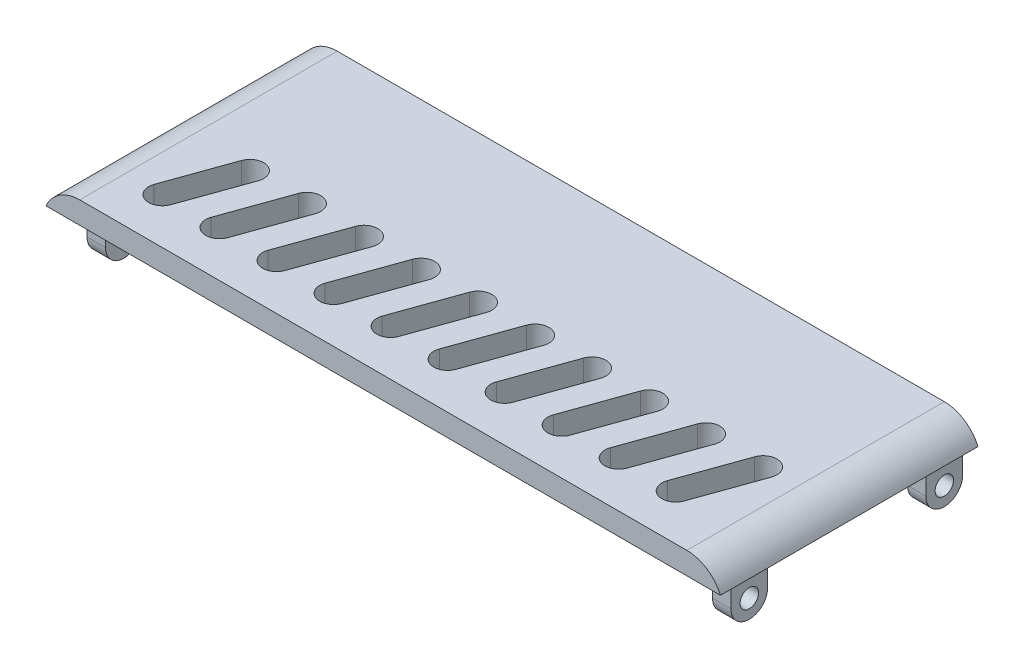
SolidWorks part; units mm, degrees
ref_plane "前视基准面" through (0, 0, 0) normal (0, 0, 1) x (1, 0, 0)
ref_plane "上视基准面" through (0, 0, 0) normal (0, 1, 0) x (1, 0, 0)
ref_plane "右视基准面" through (0, 0, 0) normal (1, 0, 0) x (0, 0, -1)
sketch "草图2" plane through (0, 0, 0) normal (0, 1, 0) x (1, 0, 0)
  line L1 (-31.0872, 15.1404) -> (42.9128, 15.1404)
  line L2 (-31.0872, 15.1404) -> (-31.0872, -12.8596)
  line L3 (-31.0872, -12.8596) -> (42.9128, -12.8596)
  line L4 (42.9128, 15.1404) -> (42.9128, -12.8596)
  dimension "D1" = 74
  dimension "D2" = 28
extrude "凸台-拉伸1" add sketch "草图2" along normal blind 4
fillet "圆角1" radius 4 2 edges at (-31.0872, 4, -1.1404) (42.9128, 4, -1.1404)
sketch "草图3" plane through (0, 0, -15.1404) normal (0, 0, -1) x (-1, 0, 0)
  line L1 (31.0872, 0) -> (-42.9128, 0)
  line L2 (31.0872, 0) -> (31.0872, 1.6)
  line L3 (31.0872, 1.6) -> (-42.9128, 1.6)
  line L4 (-42.9128, 0) -> (-42.9128, 1.6)
  dimension "D1" = 1.6
extrude "切除-拉伸1" cut sketch "草图3" against normal through all
sketch "草图15" plane through (0, 1.6, 0) normal (0, -1, 0) x (1, 0, 0)
  line L0 (33.5789, 9.0596) -> (41.4128, 9.0596)
  line L2 (45.2135, 5.0596) -> (45.2135, 10.0596)
  line L3 (45.2135, 10.0596) -> (33.5789, 10.0596)
  line L4 (33.5789, 9.0596) -> (33.5789, 10.0596)
  line L5 (42.5789, -15.1404) -> (42.5789, 12.8596) construction
  line L6 (41.4128, 9.0596) -> (41.4128, 5.0596)
  line L7 (41.4128, 5.0596) -> (45.2135, 5.0596)
  line L8 (42.9128, 14.8596) -> (42.9128, -17.1404) construction
  line L9 (-30.7532, 12.8596) -> (42.5789, 12.8596) construction
  dimension "D1" = 1
  dimension "D2" = 9
  dimension "D3" = 5
  dimension "D4" = 1.5
  dimension "D5" = 2.8
sketch "草图19" plane through (0, 4, 0) normal (0, 1, 0) x (1, 0, 0)
  line L0 (-20.5872, -0.8596) -> (-23.0872, -7.8596) construction
  line L5 (-19.1746, -1.3641) -> (-21.6746, -8.3641)
  line L8 (-21.9998, -0.3551) -> (-24.4998, -7.3551)
  line L11 (38.9128, 15.1404) -> (-27.0872, 15.1404) construction
  line L14 (-27.0872, -12.8596) -> (38.9128, -12.8596) construction
  line L17 (-14.3872, -0.8596) -> (-16.8872, -7.8596) construction
  line L20 (-12.9746, -1.3641) -> (-15.4746, -8.3641)
  line L23 (-15.7998, -0.3551) -> (-18.2998, -7.3551)
  line L26 (-40.9597, 1.1404) -> (-18.0872, 1.1404) construction
  line L27 (-27.0872, 15.1404) -> (-27.0872, -12.8596) construction
  line L28 (-8.1872, -0.8596) -> (-10.6872, -7.8596) construction
  line L31 (-6.7746, -1.3641) -> (-9.2746, -8.3641)
  line L34 (-9.5998, -0.3551) -> (-12.0998, -7.3551)
  line L37 (-1.9872, -0.8596) -> (-4.4872, -7.8596) construction
  line L40 (-0.5746, -1.3641) -> (-3.0746, -8.3641)
  line L43 (-3.3998, -0.3551) -> (-5.8998, -7.3551)
  line L46 (4.2128, -0.8596) -> (1.7128, -7.8596) construction
  line L49 (5.6254, -1.3641) -> (3.1254, -8.3641)
  line L52 (2.8002, -0.3551) -> (0.3002, -7.3551)
  line L53 (10.4128, -0.8596) -> (7.9128, -7.8596) construction
  line L54 (11.8254, -1.3641) -> (9.3254, -8.3641)
  line L55 (9.0002, -0.3551) -> (6.5002, -7.3551)
  line L56 (16.6128, -0.8596) -> (14.1128, -7.8596) construction
  line L57 (18.0254, -1.3641) -> (15.5254, -8.3641)
  line L58 (15.2002, -0.3551) -> (12.7002, -7.3551)
  line L59 (22.8128, -0.8596) -> (20.3128, -7.8596) construction
  line L60 (24.2254, -1.3641) -> (21.7254, -8.3641)
  line L61 (21.4002, -0.3551) -> (18.9002, -7.3551)
  line L62 (29.0128, -0.8596) -> (26.5128, -7.8596) construction
  line L63 (30.4254, -1.3641) -> (27.9254, -8.3641)
  line L64 (27.6002, -0.3551) -> (25.1002, -7.3551)
  line L65 (35.2128, -0.8596) -> (32.7128, -7.8596) construction
  line L66 (36.6254, -1.3641) -> (34.1254, -8.3641)
  line L67 (33.8002, -0.3551) -> (31.3002, -7.3551)
  arc A32 (-19.1746, -1.3641) -> (-21.9998, -0.3551) centre (-20.5872, -0.8596) ccw
  arc A33 (-24.4998, -7.3551) -> (-21.6746, -8.3641) centre (-23.0872, -7.8596) ccw
  arc A34 (-12.9746, -1.3641) -> (-15.7998, -0.3551) centre (-14.3872, -0.8596) ccw
  arc A35 (-18.2998, -7.3551) -> (-15.4746, -8.3641) centre (-16.8872, -7.8596) ccw
  arc A36 (-6.7746, -1.3641) -> (-9.5998, -0.3551) centre (-8.1872, -0.8596) ccw
  arc A37 (-12.0998, -7.3551) -> (-9.2746, -8.3641) centre (-10.6872, -7.8596) ccw
  arc A38 (-0.5746, -1.3641) -> (-3.3998, -0.3551) centre (-1.9872, -0.8596) ccw
  arc A39 (-5.8998, -7.3551) -> (-3.0746, -8.3641) centre (-4.4872, -7.8596) ccw
  arc A40 (5.6254, -1.3641) -> (2.8002, -0.3551) centre (4.2128, -0.8596) ccw
  arc A41 (0.3002, -7.3551) -> (3.1254, -8.3641) centre (1.7128, -7.8596) ccw
  arc A42 (11.8254, -1.3641) -> (9.0002, -0.3551) centre (10.4128, -0.8596) ccw
  arc A43 (6.5002, -7.3551) -> (9.3254, -8.3641) centre (7.9128, -7.8596) ccw
  arc A44 (18.0254, -1.3641) -> (15.2002, -0.3551) centre (16.6128, -0.8596) ccw
  arc A45 (12.7002, -7.3551) -> (15.5254, -8.3641) centre (14.1128, -7.8596) ccw
  arc A46 (24.2254, -1.3641) -> (21.4002, -0.3551) centre (22.8128, -0.8596) ccw
  arc A47 (18.9002, -7.3551) -> (21.7254, -8.3641) centre (20.3128, -7.8596) ccw
  arc A48 (30.4254, -1.3641) -> (27.6002, -0.3551) centre (29.0128, -0.8596) ccw
  arc A49 (25.1002, -7.3551) -> (27.9254, -8.3641) centre (26.5128, -7.8596) ccw
  arc A50 (36.6254, -1.3641) -> (33.8002, -0.3551) centre (35.2128, -0.8596) ccw
  arc A51 (31.3002, -7.3551) -> (34.1254, -8.3641) centre (32.7128, -7.8596) ccw
  point P2 (-21.8372, -4.3596)
  point P15 (-15.6372, -4.3596)
  point P22 (-9.4372, -4.3596)
  point P29 (-3.2372, -4.3596)
  point P36 (2.9628, -4.3596)
  point P43 (9.1628, -4.3596)
  point P50 (15.3628, -4.3596)
  point P57 (21.5628, -4.3596)
  point P64 (-27.0872, 1.1404)
  point P68 (27.7628, -4.3596)
  point P75 (33.9628, -4.3596)
  dimension "D6" = 4
  dimension "D3" = 1.5
  dimension "D1" = 16
  dimension "D2" = 5
  dimension "D4" = 6.5
  dimension "D5" = 10
extrude "切除-拉伸6" cut sketch "草图19" against normal up to next
sketch "草图21" plane through (0, 1.6, 0) normal (0, -1, 0) x (1, 0, 0)
  line L1 (-22.7532, 12.0596) -> (-12.7532, 12.0596)
  line L2 (-22.7532, 12.0596) -> (-22.7532, 10.0596)
  line L3 (-22.7532, 10.0596) -> (-12.7532, 10.0596)
  line L4 (-12.7532, 12.0596) -> (-12.7532, 10.0596)
  line L5 (30.5789, 10.0596) -> (18.5789, 10.0596)
  line L6 (30.5789, 10.0596) -> (30.5789, 12.0596)
  line L7 (30.5789, 12.0596) -> (18.5789, 12.0596)
  line L8 (18.5789, 10.0596) -> (18.5789, 12.0596)
  line L12 (-30.7532, 12.8596) -> (-30.7532, -15.1404) construction
  dimension "D1" = 2
  dimension "D2" = 8
  dimension "D3" = 10
  dimension "D4" = 12
extrude "凸台-拉伸9" add sketch "草图21" along normal blind 0.15
sketch "草图22" plane through (0, 1.6, 0) normal (0, -1, 0) x (1, 0, 0)
  line L1 (-29.0872, 10.0596) -> (-27.0872, 10.0596)
  line L2 (-29.0872, 10.0596) -> (-29.0872, 6.0596)
  line L3 (-29.0872, 6.0596) -> (-27.0872, 6.0596)
  line L4 (-27.0872, 10.0596) -> (-27.0872, 6.0596)
  line L5 (-29.0872, -1.1802) -> (-29.0872, -15.1404) construction
  line L6 (-29.0872, -11.1404) -> (-27.0872, -11.1404)
  line L7 (-29.0872, -11.1404) -> (-29.0872, -15.1404)
  line L8 (-29.0872, -15.1404) -> (-27.0872, -15.1404)
  line L9 (-27.0872, -11.1404) -> (-27.0872, -15.1404)
  line L10 (-30.7532, -15.1404) -> (42.5789, -15.1404) construction
  line L11 (-30.7532, 12.8596) -> (42.5789, 12.8596) construction
  line L12 (40.9128, -15.1404) -> (40.9128, -1.1802) construction
  line L13 (40.9128, 10.0596) -> (38.9128, 10.0596)
  line L14 (40.9128, 10.0596) -> (40.9128, 6.0596)
  line L15 (40.9128, 6.0596) -> (38.9128, 6.0596)
  line L16 (38.9128, 10.0596) -> (38.9128, 6.0596)
  line L17 (40.9128, -15.1404) -> (38.9128, -15.1404)
  line L18 (40.9128, -15.1404) -> (40.9128, -11.1404)
  line L19 (40.9128, -11.1404) -> (38.9128, -11.1404)
  line L20 (38.9128, -15.1404) -> (38.9128, -11.1404)
  line L21 (40.9128, 5.8198) -> (40.9128, 12.8596) construction
  line L22 (-29.0872, 12.8596) -> (-29.0872, 5.8198) construction
  point P4 (-29.0872, 12.8596)
  point P21 (0, 0)
  point P25 (0, 0)
  point P26 (0, 0)
  point P27 (40.9128, 9.9538)
  point P28 (40.9128, 10.0899)
  point P29 (40.9128, 8.8596)
  point P30 (0, 0)
  point P33 (0, 0)
  point P37 (0, 0)
  point P38 (-29.0872, 11.7548)
  dimension "D1" = 4
  dimension "D2" = 2
  dimension "D3" = 2.8
extrude "凸台-拉伸10" add sketch "草图22" along normal blind 5.5
fillet "圆角3" radius 2 8 edges at (-28.0872, -3.9, -15.1404) (-28.0872, -3.9, -11.1404) (-28.0872, -3.9, 6.0596) (-28.0872, -3.9, 10.0596) (39.9128, -3.9, -11.1404) (39.9128, -3.9, -15.1404) (39.9128, -3.9, 6.0596) (39.9128, -3.9, 10.0596)
sketch "草图23" plane through (-29.0872, 0, 0) normal (-1, 0, 0) x (0, 0, 1)
  circle A0 centre (8.0596, -1.9) radius 1
  circle A1 centre (-13.1404, -1.9) radius 1
  dimension "D1" = 2
extrude "切除-拉伸8" cut sketch "草图23" against normal blind 2 draft 2
sketch "草图24" plane through (40.9128, 0, 0) normal (1, 0, 0) x (0, 0, -1)
  circle A0 centre (13.1404, -1.9) radius 1 construction
  circle A2 centre (13.1404, -1.9) radius 1
  circle A3 centre (-8.0596, -1.9) radius 1
  point P2 (-10.8596, -1.9)
  point P3 (-8.0596, -1.9)
  point P6 (0, 0)
  point P7 (-10.8596, -1.9)
  point P8 (0, 0)
extrude "切除-拉伸9" cut sketch "草图24" against normal blind 2 draft 2
sketch "草图25" plane through (0, 1.6, 0) normal (0, -1, 0) x (1, 0, 0)
  line L1 (-27.0872, 10.0596) -> (-21.0872, 10.0596)
  line L2 (-27.0872, 10.0596) -> (-27.0872, 8.8596)
  line L3 (-27.0872, 8.8596) -> (-21.0872, 8.8596)
  line L4 (-21.0872, 10.0596) -> (-21.0872, 8.8596)
  line L5 (38.9128, 10.0596) -> (34.9128, 10.0596)
  line L6 (38.9128, 10.0596) -> (38.9128, 8.8596)
  line L7 (38.9128, 8.8596) -> (34.9128, 8.8596)
  line L8 (34.9128, 10.0596) -> (34.9128, 8.8596)
  line L10 (38.9128, 8.0596) -> (38.9128, 6.0596) construction
  point P4 (0, 0)
  point P9 (0, 0)
  point P10 (0, 0)
  dimension "D1" = 1.2
  dimension "D2" = 6
  dimension "D3" = 4
extrude "凸台-拉伸11" add sketch "草图25" along normal blind 3
chamfer "倒角1" distance 1 angle 33 2 edges at (36.9128, -1.4, 10.0596) (-24.0872, -1.4, 10.0596) first distance on face at (38.2462, -0.5667, 10.0596) first distance on face at (-25.0037, -0.0625, 10.0596)
